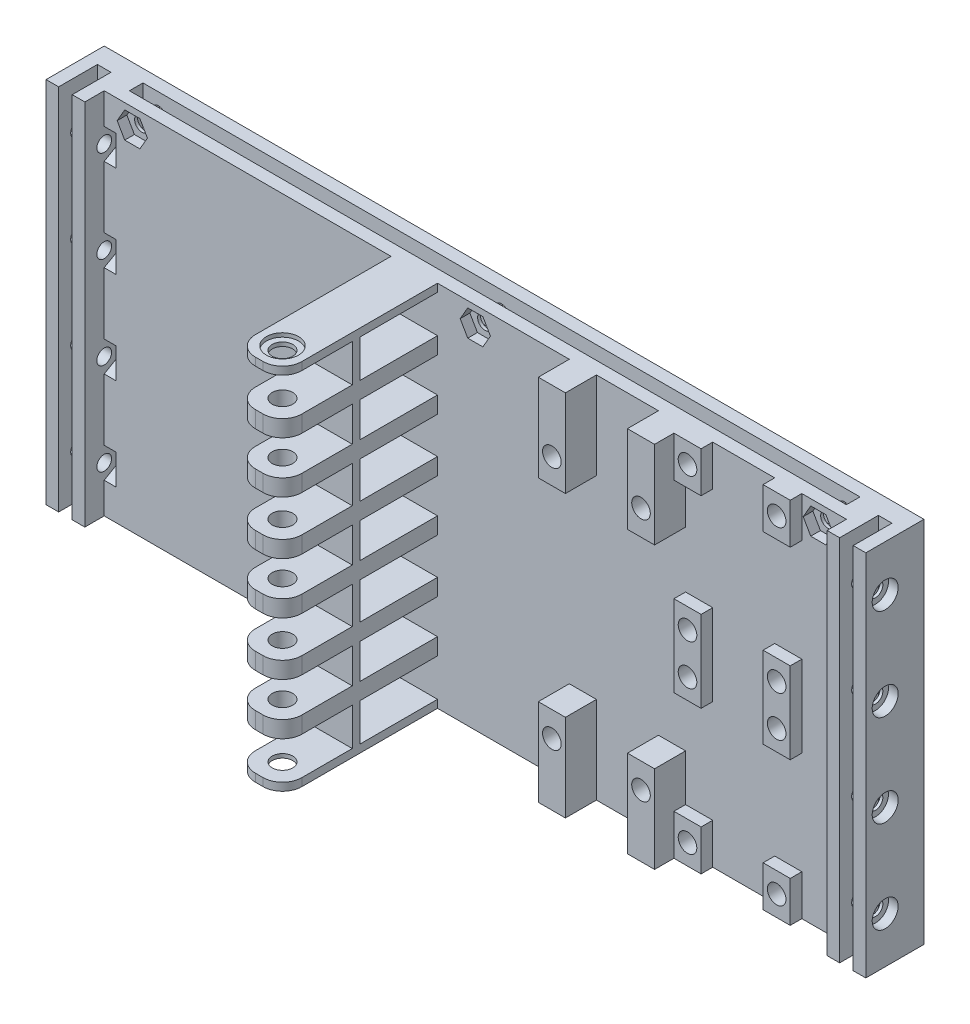
SolidWorks part; units mm, degrees
ref_plane "Front Plane" through (0, 0, 0) normal (1, 0, 0) x (0, 1, 0)
ref_plane "Top Plane" through (0, 0, 0) normal (0, 0, 1) x (0, 1, 0)
ref_plane "Right Plane" through (0, 0, 0) normal (0, 1, 0) x (-1, 0, 0)
sketch "Sketch1" plane through (0, 0, 0) normal (0, 0, 1) x (0, 1, 0)
  line L1 (0, 0) -> (-95, 0)
  line L2 (0, 0) -> (0, 12)
  line L3 (0, 12) -> (-95, 12)
  line L4 (-95, 0) -> (-95, 12)
extrude "Boss-Extrude1" add sketch "Sketch1" along normal blind 10 contours L3 L4 L1 L2
sketch "Sketch3" plane through (0, 0, 10) normal (0, 0, 1) x (1, 0, 0)
  line L0 (0, 0) -> (0, -95) construction
  line L1 (-12, 0) -> (0, 0)
  line L2 (-12, 0) -> (-12, -2.025)
  line L3 (-12, -2.025) -> (0, -2.025)
  line L4 (0, 0) -> (0, -2.025)
  line L6 (-12, -2.025) -> (0, -2.025) construction
  line L8 (-12, -11.725) -> (0, -11.725) construction
  line L10 (-12, -11.725) -> (0, -11.725)
  line L11 (-12, -11.725) -> (-12, -16.025)
  line L12 (-12, -16.025) -> (0, -16.025)
  line L13 (0, -11.725) -> (0, -16.025)
  line L14 (-12, -16.025) -> (0, -16.025) construction
  line L16 (-12, -24.975) -> (0, -24.975) construction
  line L18 (0, -24.975) -> (-12, -24.975)
  line L19 (0, -24.975) -> (0, -29.275)
  line L20 (0, -29.275) -> (-12, -29.275)
  line L21 (-12, -24.975) -> (-12, -29.275)
  line L23 (-12, -29.275) -> (0, -29.275) construction
  line L25 (-12, -38.725) -> (0, -38.725) construction
  line L27 (-12, -38.725) -> (0, -38.725)
  line L28 (-12, -38.725) -> (-12, -43.025)
  line L29 (-12, -43.025) -> (0, -43.025)
  line L30 (0, -38.725) -> (0, -43.025)
  dimension "D1" = 2.025
  dimension "D2" = 9.7
  dimension "D3" = 4.3
  dimension "D4" = 8.95
  dimension "D5" = 4.3
  dimension "D6" = 9.45
  dimension "D7" = 4.3
extrude "Boss-Extrude2" add sketch "Sketch3" along normal blind 40
fillet "Fillet1" radius 5 8 edges at (-12, -1.0125, 50) (0, -1.0125, 50) (-12, -13.875, 50) (0, -13.875, 50) (-12, -40.875, 50) (-12, -27.125, 50) (0, -27.125, 50) (0, -40.875, 50)
ref_plane "Plane1" through (0, -47.5, 0) normal (0, 1, 0) x (1, 0, 0)
mirror "Mirror1" about plane through (0, -47.5, 0) normal (0, 1, 0) of "Fillet1", "Boss-Extrude2"
sketch "Sketch5" plane through (0, 0, 0) normal (0, 1, 0) x (-1, 0, 0)
  line L0 (5, 50) -> (7, 50) construction
  line L1 (6, 50) -> (0, 50)
  line L2 (6, 50) -> (6, 44)
  line L3 (6, 44) -> (0, 44)
  line L4 (0, 50) -> (0, 44)
  circle A0 centre (6, 44) radius 2.65
  dimension "D2" = 5.3
  dimension "D1" = 6
extrude "Cut-Extrude1" cut sketch "Sketch5" against normal through all contours A0
sketch "Sketch7" plane through (0, 0, 0) normal (0, 1, 0) x (-1, 0, 0)
  line L0 (5, 50) -> (7, 50) construction
  line L1 (6, 50) -> (0, 50)
  line L2 (6, 50) -> (6, 44)
  line L3 (6, 44) -> (0, 44)
  line L4 (0, 50) -> (0, 44)
  line L5 (0, 45) -> (0, 0) construction
  circle A0 centre (6, 44) radius 4.15
  circle M6 centre (6, 44) radius 2.65
  dimension "D1" = 6
  dimension "D2" = 8.3
extrude "Cut-Extrude2" cut sketch "Sketch7" against normal blind 1 contours L3 A0 L2 M6 | L2 A0 L3 M6
mirror "Mirror2" about plane through (0, -47.5, 0) normal (0, 1, 0) of "Cut-Extrude2"
sketch "Sketch8" plane through (0, 0, 0) normal (0, 0, -1) x (1, 0, 0)
  line L0 (0, 95) -> (-12, 95) construction
  line L1 (-6, 95) -> (-96, 95)
  line L2 (-6, 95) -> (-6, 0)
  line L3 (-6, 0) -> (-96, 0)
  line L4 (-96, 95) -> (-96, 0)
  line L5 (-6, 95) -> (115.5, 95)
  line L6 (-6, 95) -> (-6, 0)
  line L7 (-6, 0) -> (115.5, 0)
  line L8 (115.5, 95) -> (115.5, 0)
  line L9 (0, 0) -> (-12, 0) construction
  line M2 (0, 0) -> (0, 95)
  line M4 (-12, 95) -> (-12, 0)
  dimension "D1" = 121.5
  dimension "D2" = 90
extrude "Boss-Extrude3" add sketch "Sketch8" against normal blind 10 contours L1 L4 L3 M4 | L8 L5 L7 M2
sketch "Sketch9" plane through (0, 0, 10) normal (0, 0, 1) x (1, 0, 0)
  line L0 (0, -95) -> (115.5, -95) construction
  line L1 (115.5, 0) -> (105.5, 0)
  line L2 (115.5, 0) -> (115.5, -95)
  line L3 (115.5, -95) -> (105.5, -95)
  line L4 (105.5, 0) -> (105.5, -95)
  line L5 (-12, -95) -> (-96, -95) construction
  line L6 (-96, 0) -> (-86, 0)
  line L7 (-96, 0) -> (-96, -95)
  line L8 (-96, -95) -> (-86, -95)
  line L9 (-86, 0) -> (-86, -95)
  dimension "D1" = 10
  dimension "D2" = 10
extrude "Boss-Extrude4" add sketch "Sketch9" along normal blind 5
sketch "Sketch12" plane through (-12, 0, 0) normal (-1, 0, 0) x (0, -1, 0)
  line L1 (0, 12) -> (95, 12)
  line L2 (0, 12) -> (0, 10)
  line L3 (0, 10) -> (95, 10)
  line L4 (95, 12) -> (95, 10)
  line L5 (95, 45) -> (95, 10) construction
  dimension "D1" = 2
sketch "Sketch11" plane through (0, 0, 15) normal (0, 0, 1) x (1, 0, 0)
  line L0 (110.5, 0) -> (110.5, -95) construction
  line L1 (115.5, 0) -> (105.5, 0) construction
  line L2 (105.5, -95) -> (115.5, -95) construction
  line L3 (110.5, -10) -> (110.5, -30) construction
  line L4 (112.5, -10) -> (112.5, -30)
  line L5 (108.5, -10) -> (108.5, -30)
  line L7 (115.5, 0) -> (110.5, 0)
  line L8 (115.5, 0) -> (115.5, -10)
  line L9 (115.5, -10) -> (110.5, -10)
  line L10 (110.5, 0) -> (110.5, -10)
  arc A0 (112.5, -10) -> (108.5, -10) centre (110.5, -10) ccw
  arc A1 (108.5, -30) -> (112.5, -30) centre (110.5, -30) ccw
  point P8 (110.5, -20)
  dimension "D1" = 10
  dimension "D2" = 20
extrude "Cut-Extrude3" [suppressed] cut sketch "Sketch11" against normal blind 10 contours L4 A1 L5 A0
pattern_linear "LPattern1" [suppressed] count 2 spacing 55
extrude "Boss-Extrude5" [suppressed] add sketch "Sketch12" along normal up to next
sketch "Sketch13" plane through (0, -95, 0) normal (0, 1, 0) x (-1, 0, 0)
  line L1 (0, 10) -> (12, 10)
  line L2 (0, 10) -> (0, 30)
  line L3 (0, 30) -> (12, 30)
  line L4 (12, 10) -> (12, 30)
  line L5 (12, 45) -> (12, 10) construction
  line L6 (0, 30) -> (12, 30)
  line L7 (0, 30) -> (0, 32)
  line L8 (0, 32) -> (12, 32)
  line L9 (12, 30) -> (12, 32)
  dimension "D1" = 20
  dimension "D2" = 2
extrude "Boss-Extrude6" add sketch "Sketch13" along normal through all contours L7 L6 L9 L8
sketch "Sketch14" plane through (0, 0, 0) normal (0, 1, 0) x (-1, 0, 0)
  line L0 (-115.5, 0) -> (96, 0) construction
  line L1 (86, 0) -> (-105.5, 0)
  line L2 (86, 0) -> (86, 10)
  line L3 (86, 10) -> (-105.5, 10)
  line L4 (-105.5, 0) -> (-105.5, 10)
  line L5 (82.75, 6.75) -> (-102.25, 6.75)
  line L6 (-102.25, 3.25) -> (-102.25, 6.75)
  line L7 (82.75, 3.25) -> (-102.25, 3.25)
  line L8 (82.75, 3.25) -> (82.75, 6.75)
  line L9 (96, 15) -> (96, 0) construction
  line L12 (96, 0) -> (86, 0)
  line L13 (96, 0) -> (96, 10)
  line L14 (96, 10) -> (86, 10)
  line L15 (86, 0) -> (86, 10)
  dimension "D1" = 3.25
extrude "Cut-Extrude4" cut sketch "Sketch14" against normal blind 10 contours L7 L8 L5 L6
mirror "Mirror3" about plane through (0, -47.5, 0) normal (0, 1, 0) of "Cut-Extrude4"
sketch "Sketch15" plane through (19.6145, 61.4983, 10) normal (0, 0, 1) x (1, 0, 0)
  line L1 (-105.6145, -61.4983) -> (-98.3645, -61.4983)
  line L2 (-105.6145, -61.4983) -> (-105.6145, -66.4983)
  line L3 (-105.6145, -66.4983) -> (-98.3645, -66.4983)
  line L4 (-98.3645, -61.4983) -> (-98.3645, -66.4983)
  circle A0 centre (-98.3645, -66.4983) radius 1.9
  circle A1 centre (-98.3645, -66.4983) radius 3.15
  dimension "D3" = 3.8
  dimension "D4" = 6.3
  dimension "D1" = 7.25
extrude "Cut-Extrude5" cut sketch "Sketch15" against normal through all contours A0
sketch "Sketch16" plane through (-19.6145, 61.4983, 0) normal (0, 0, -1) x (-1, 0, 0)
  circle A2 centre (59.1355, -66.4983) radius 3.35
  dimension "D1" = 6.7
extrude "Cut-Extrude6" cut sketch "Sketch16" against normal blind 2.5
sketch "Sketch17" plane through (19.6145, 61.4983, 10) normal (0, 0, 1) x (1, 0, 0)
  line L0 (-94.4604, -66.4983) -> (-96.4124, -63.1172)
  line L1 (-94.8645, -66.4983) -> (-96.6145, -63.4672)
  line L2 (-96.6145, -63.4672) -> (-100.1145, -63.4672)
  line L3 (-100.1145, -63.4672) -> (-101.8645, -66.4983)
  line L4 (-101.8645, -66.4983) -> (-100.1145, -69.5293)
  line L5 (-100.1145, -69.5293) -> (-96.6145, -69.5293)
  line L6 (-96.6145, -69.5293) -> (-94.8645, -66.4983)
  line L7 (-96.4124, -63.1172) -> (-100.3166, -63.1172)
  line L8 (-100.3166, -63.1172) -> (-102.2687, -66.4983)
  line L9 (-102.2687, -66.4983) -> (-100.3166, -69.8793)
  line L10 (-100.3166, -69.8793) -> (-96.4124, -69.8793)
  line L11 (-96.4124, -69.8793) -> (-94.4604, -66.4983)
  line L13 (-31.6145, -61.4983) -> (-105.6145, -61.4983) construction
  circle A0 centre (-98.3645, -66.4983) radius 3.0311 construction
  dimension "D1" = 3.5
  dimension "D2" = 0.35
extrude "Cut-Extrude7" cut sketch "Sketch17" against normal blind 2.5
pattern_linear "LPattern2" count 3 spacing 88.5 along (1, 0, 0) of "Cut-Extrude7", "Cut-Extrude6", "Cut-Extrude5"
sketch "Sketch18" plane through (0, 0, 10) normal (0, 0, 1) x (1, 0, 0)
  line L0 (0, -95) -> (105.5, -95) construction
  line L1 (105.5, 0) -> (94, 0)
  line L2 (105.5, 0) -> (105.5, -95)
  line L3 (105.5, -95) -> (94, -95)
  line L4 (94, 0) -> (94, -95)
  line L6 (94, 0) -> (87, 0)
  line L7 (94, 0) -> (94, -95)
  line L8 (94, -95) -> (87, -95)
  line L9 (87, 0) -> (87, -95)
  line L10 (87, 0) -> (71, 0)
  line L11 (87, 0) -> (87, -95)
  line L12 (87, -95) -> (71, -95)
  line L13 (71, 0) -> (71, -95)
  line L14 (71, 0) -> (64, 0)
  line L15 (71, 0) -> (71, -95)
  line L16 (71, -95) -> (64, -95)
  line L17 (64, 0) -> (64, -95)
  line L20 (64, 0) -> (64, -95)
  dimension "D1" = 11.5
  dimension "D2" = 7
  dimension "D3" = 16
  dimension "D4" = 7
extrude "Boss-Extrude7" add sketch "Sketch18" along normal blind 3
sketch "Sketch19" plane through (0, 0, 10) normal (0, 0, 1) x (1, 0, 0)
  line L0 (71, -95) -> (64, -95) construction
  line L4 (64, 0) -> (64, -95)
  line L6 (64, 0) -> (57, 0)
  line L7 (64, 0) -> (64, -95)
  line L8 (64, -95) -> (57, -95)
  line L9 (57, 0) -> (57, -95)
  line L10 (57, 0) -> (41, 0)
  line L11 (57, 0) -> (57, -95)
  line L12 (57, -95) -> (41, -95)
  line L13 (41, 0) -> (41, -95)
  line L14 (41, 0) -> (34, 0)
  line L15 (41, 0) -> (41, -95)
  line L16 (41, -95) -> (34, -95)
  line L17 (34, 0) -> (34, -95)
  line L18 (64, 0) -> (64, -95) construction
  dimension "D2" = 7
  dimension "D3" = 16
  dimension "D4" = 7
extrude "Boss-Extrude8" add sketch "Sketch19" along normal blind 8
sketch "Sketch20" plane through (0, 0, 0) normal (0, 1, 0) x (-1, 0, 0)
  line L0 (-112.25, 5) -> (-108.75, 5)
  line L1 (-115.5, 15) -> (-112.25, 15)
  line L2 (-115.5, 15) -> (-115.5, 5)
  line L3 (-115.5, 5) -> (-112.25, 5)
  line L4 (-112.25, 15) -> (-112.25, 5)
  line L5 (-105.5, 15) -> (-108.75, 15)
  line L6 (-105.5, 15) -> (-105.5, 5)
  line L7 (-105.5, 5) -> (-108.75, 5)
  line L8 (-108.75, 15) -> (-108.75, 5)
  dimension "D1" = 10
  dimension "D2" = 3.25
  dimension "D3" = 3.25
  dimension "D4" = 10
extrude "Cut-Extrude8" cut sketch "Sketch20" against normal up to next
pattern_linear "LPattern3" count 2 spacing 201.5 along (-1, 0, 0) of "Cut-Extrude8"
sketch "Sketch21" plane through (0, 0, 13) normal (0, 0, 1) x (1, 0, 0)
  line L1 (94, 0) -> (90.5, 0)
  line L2 (94, 0) -> (94, -5.25)
  line L3 (94, -5.25) -> (90.5, -5.25)
  line L4 (90.5, 0) -> (90.5, -5.25)
  line L5 (94, 0) -> (87, 0) construction
  circle A0 centre (90.5, -5.25) radius 2.4
  dimension "D2" = 4.8
  dimension "D1" = 5.25
extrude "Cut-Extrude9" cut sketch "Sketch21" against normal blind 3.8 contours A0
sketch "Sketch22" plane through (0, 0, 9.2) normal (0, 0, 1) x (1, 0, 0)
  circle A0 centre (90.5, -5.25) radius 1.75
  dimension "D1" = 3.5
extrude "Cut-Extrude10" cut sketch "Sketch22" against normal blind 0.6 contours A0
sketch "Sketch23" plane through (0, 0, 18) normal (0, 0, 1) x (1, 0, 0)
  line L0 (64, 0) -> (57, 0) construction
  line L1 (64, 0) -> (60.5, 0)
  line L2 (64, 0) -> (64, -16)
  line L3 (64, -16) -> (60.5, -16)
  line L4 (60.5, 0) -> (60.5, -16)
  line L6 (64, -95) -> (64, 0) construction
  circle A0 centre (60.5, -16) radius 2.4
  dimension "D2" = 4.8
  dimension "D1" = 16
extrude "Cut-Extrude11" cut sketch "Sketch23" against normal blind 3.8 contours A0
sketch "Sketch24" plane through (0, 0, 14.2) normal (0, 0, 1) x (1, 0, 0)
  circle A0 centre (60.5, -16) radius 1.75
  dimension "D1" = 3.5
extrude "Cut-Extrude12" cut sketch "Sketch24" against normal blind 0.6 contours A0
pattern_linear "LPattern4" count 2 spacing 23 along (-1, 0, 0) count 2 spacing 37 along (0, -1, 0) of "Cut-Extrude10", "Cut-Extrude9"
pattern_linear "LPattern5" count 2 spacing 23 along (-1, 0, 0) of "Cut-Extrude11", "Cut-Extrude12"
mirror "Mirror4" about plane through (0, -47.5, 0) normal (0, 1, 0) of "LPattern5", "LPattern4", "Cut-Extrude9", "Cut-Extrude10", "Cut-Extrude11", "Cut-Extrude12"
sketch "Sketch25" plane through (115.5, 0, 0) normal (1, 0, 0) x (0, 1, 0)
  line L1 (0, 15) -> (-11.875, 15)
  line L2 (0, 15) -> (0, 10)
  line L3 (0, 10) -> (-11.875, 10)
  line L4 (-11.875, 15) -> (-11.875, 10)
  circle A0 centre (-11.875, 10) radius 1.9
  dimension "D2" = 3.8
  dimension "D3" = 11.875
extrude "Cut-Extrude13" cut sketch "Sketch25" against normal blind 10 contours A0
sketch "Sketch26" plane through (115.5, 0, 0) normal (1, 0, 0) x (0, 1, 0)
  circle A0 centre (-11.875, 10) radius 3.35
  dimension "D1" = 6.7
extrude "Cut-Extrude14" cut sketch "Sketch26" against normal blind 2.5
sketch "Sketch27" plane through (105.5, 0, 0) normal (-1, 0, 0) x (0, -1, 0)
  line L0 (0, 15) -> (95, 15) construction
  line L1 (10.125, 13.0311) -> (8.375, 10)
  line L2 (8.375, 10) -> (10.125, 6.9689)
  line L3 (10.125, 6.9689) -> (13.625, 6.9689)
  line L4 (13.625, 6.9689) -> (15.375, 10)
  line L5 (15.375, 10) -> (13.625, 13.0311)
  line L6 (13.625, 13.0311) -> (10.125, 13.0311)
  line L7 (9.9229, 13.3811) -> (7.9709, 10)
  line L8 (7.9709, 10) -> (9.9229, 6.6189)
  line L9 (9.9229, 6.6189) -> (13.8271, 6.6189)
  line L10 (13.8271, 6.6189) -> (15.7791, 10)
  line L11 (15.7791, 10) -> (13.8271, 13.3811)
  line L12 (13.8271, 13.3811) -> (9.9229, 13.3811)
  circle A0 centre (11.875, 10) radius 3.0311 construction
  dimension "D1" = 3.5
  dimension "D2" = 0.35
extrude "Cut-Extrude15" cut sketch "Sketch27" along normal blind 3 contours L11 L12 L7 L8 L9 L10
pattern_linear "LPattern6" count 4 spacing 23.75 along (0, -1, 0) of "Cut-Extrude14", "Cut-Extrude15", "Cut-Extrude13"
ref_plane "Plane2" through (9.75, 0, 0) normal (1, 0, 0) x (0, 0, -1)
mirror "Mirror5" about plane through (9.75, 0, 0) normal (1, 0, 0) of "LPattern6", "Cut-Extrude13", "Cut-Extrude14", "Cut-Extrude15"
sketch "Sketch28" plane through (34, 0, 0) normal (-1, 0, 0) x (0, -1, 0)
  line L0 (0, 10) -> (95, 10) construction
  line L1 (0, 18) -> (22.5, 18)
  line L2 (0, 18) -> (0, 10)
  line L3 (0, 10) -> (22.5, 10)
  line L4 (22.5, 18) -> (22.5, 10)
  line L6 (22.5, 18) -> (72.5, 18)
  line L8 (22.5, 10) -> (72.5, 10)
  line L9 (72.5, 18) -> (72.5, 10)
  line L10 (72.5, 18) -> (95, 18)
  line L12 (72.5, 10) -> (95, 10)
  line L13 (95, 18) -> (95, 10)
  line M6 (0, 10) -> (95, 10)
  line M8 (95, 18) -> (0, 18)
  dimension "D1" = 22.5
  dimension "D2" = 22.5
extrude "Cut-Extrude16" cut sketch "Sketch28" against normal blind 30 contours L9 L4 M8 M6
sketch "Sketch29" plane through (64, 0, 0) normal (-1, 0, 0) x (0, -1, 0)
  line L0 (0, 13) -> (95, 13) construction
  line L1 (0, 10) -> (10.5, 10)
  line L2 (0, 10) -> (0, 13)
  line L3 (0, 13) -> (10.5, 13)
  line L4 (10.5, 10) -> (10.5, 13)
  line L6 (10.5, 13) -> (37, 13)
  line L7 (10.5, 13) -> (10.5, 10)
  line L8 (10.5, 10) -> (37, 10)
  line L9 (37, 13) -> (37, 10)
  line L10 (0, 10) -> (95, 10) construction
  line L11 (37, 13) -> (58, 13)
  line L12 (37, 13) -> (37, 10)
  line L13 (37, 10) -> (58, 10)
  line L14 (58, 13) -> (58, 10)
  line L15 (58, 13) -> (84.5, 13)
  line L16 (58, 13) -> (58, 10)
  line L17 (58, 10) -> (84.5, 10)
  line L18 (84.5, 13) -> (84.5, 10)
  line L20 (84.5, 13) -> (95, 13)
  line L21 (84.5, 13) -> (84.5, 10)
  line L22 (84.5, 10) -> (95, 10)
  line L23 (95, 13) -> (95, 10)
  line M15 (22.5, 13) -> (22.5, 10)
  line M16 (22.5, 10) -> (72.5, 10)
  line M17 (72.5, 10) -> (72.5, 13)
  line M18 (72.5, 13) -> (22.5, 13)
  dimension "D1" = 10.5
  dimension "D2" = 10.5
  dimension "D3" = 26.5
  dimension "D4" = 26.5
extrude "Cut-Extrude17" cut sketch "Sketch29" against normal blind 30 contours L4 L8 L6 M15 | L9 M18 M15 M16 | L18 L15 L17 M17 | L14 M18 M16 M17
equation "\"whitekey_cutout_length\"= 101.5"
equation "\"wall_thickness\"=10"
equation "\"D1@Sketch9\"=\"wall_thickness\""
equation "\"D2@Sketch9\"=\"wall_thickness\""
equation "\"D1@Boss-Extrude3\"=\"wall_thickness\""
equation "\"base_mount_height\"=40"
equation "\"D1@Boss-Extrude2\"=\"base_mount_height\""
equation "\"base_rear_length\"=80"
equation "\"D1@Sketch8\"=\"wall_thickness\"+110+1.5"
equation "\"D2@Sketch8\"=\"base_rear_length\"+\"wall_thickness\""
equation "\"key_mount_recess_length\"=50"
equation "\"key_mount_recess_height\"=12.5"
equation "\"key_mount_recess_depth\"=1.5"
equation "\"guide_brace_height\"=20"
equation "\"guide_brace_thickness\"=2"
equation "\"dowel_recess_depth\"=10"
equation "\"dowel_recess_offset\"=3.25"
equation "\"base_front_length\"=111.5"
equation "\"screw_hole_wall_offset\"=7.25"
equation "\"screw_hole_edge_inset\"=\"dowel_recess_depth\"/2"
equation "\"screw_hole_diameter\"=3.8"
equation "\"screw_head_hole_diameter\"=6.7"
equation "\"screw_nut_hole_side_len\"=3.5"
equation "\"screw_nut_recess_offset\"=0.35"
equation "\"screw_head_and_nut_recess_depth\"=2.5"
equation "\"screw_shaft_diameter\"=3.5"
equation "\"switch_board_width\"=30"
equation "\"switch_board_thickness\"=1.6"
equation "\"switch_board_wall_offset\"=11.5"
equation "\"heatset_insert_hole_diameter\"=4.8"
equation "\"heatset_insert_hole_depth\"=3.8"
equation "\"front_rear_panel_width\"=23.75"
equation "\"rod_length_adj\"=0.5"
equation "\"rod_insert_length\"=2.8"
equation "\"D1@Sketch14\"=\"dowel_recess_offset\""
equation "\"D1@Cut-Extrude4\"=\"dowel_recess_depth\""
equation "\"D1@Sketch13\"=\"guide_brace_height\""
equation "\"D2@Sketch13\"=\"guide_brace_thickness\""
equation "\"D1@Sketch15\"=\"screw_hole_wall_offset\""
equation "\"D2@Sketch15\"=\"screw_hole_edge_inset\""
equation "\"D3@Sketch15\"=\"screw_hole_diameter\""
equation "\"D1@Sketch16\"=\"screw_head_hole_diameter\""
equation "\"D1@Cut-Extrude6\"=\"screw_head_and_nut_recess_depth\""
equation "\"D1@Sketch17\"=\"screw_nut_hole_side_len\""
equation "\"D2@Sketch17\"=\"screw_nut_recess_offset\""
equation "\"D3@LPattern2\"=0.5*(\"base_front_length\"+\"base_rear_length\"-\"screw_hole_wall_offset\"*2)"
equation "\"D1@Sketch18\"=\"switch_board_wall_offset\""
equation "\"D2@Sketch18\"=\"screw_shaft_diameter\"*2"
equation "\"D3@Sketch18\"=\"switch_board_width\"-\"screw_shaft_diameter\"*4"
equation "\"D4@Sketch18\"=\"screw_shaft_diameter\"*2"
equation "\"D1@Boss-Extrude7\"=\"switch_white_key_mount_height\""
equation "\"D2@Sketch19\"=\"screw_shaft_diameter\"*2"
equation "\"D3@Sketch19\"=\"switch_board_width\"-\"screw_shaft_diameter\"*4"
equation "\"D4@Sketch19\"=\"screw_shaft_diameter\"*2"
equation "\"D1@Boss-Extrude8\"=\"switch_black_key_mount_height\""
equation "\"switch_black_key_mount_height\"=8"
equation "\"switch_white_key_mount_height\"=3"
equation "\"D1@Sketch20\"=\"dowel_recess_depth\""
equation "\"D2@Sketch20\"=\"dowel_recess_offset\""
equation "\"D3@Sketch20\"=\"dowel_recess_offset\""
equation "\"D4@Sketch20\"=\"dowel_recess_depth\""
equation "\"D3@LPattern3\"=\"base_front_length\"+\"base_rear_length\"+\"wall_thickness\""
equation "\"D2@Sketch21\"=\"heatset_insert_hole_diameter\""
equation "\"D1@Cut-Extrude9\"=\"heatset_insert_hole_depth\""
equation "\"D1@Sketch22\"=\"screw_shaft_diameter\""
equation "\"D1@Cut-Extrude10\"=6-\"heatset_insert_hole_depth\"-\"switch_board_thickness\""
equation "\"D2@Sketch23\"=\"heatset_insert_hole_diameter\""
equation "\"D1@Cut-Extrude11\"=\"heatset_insert_hole_depth\""
equation "\"D1@Sketch24\"=\"screw_shaft_diameter\""
equation "\"D1@Cut-Extrude12\"=6-\"heatset_insert_hole_depth\"-\"switch_board_thickness\""
equation "\"D3@LPattern4\"=\"switch_board_width\"-\"screw_shaft_diameter\"*2"
equation "\"D3@LPattern5\"=\"switch_board_width\"-\"screw_shaft_diameter\"*2"
equation "\"D1@Sketch25\"=\"screw_hole_edge_inset\""
equation "\"D3@Sketch25\"=\"front_rear_panel_width\"/2"
equation "\"D2@Sketch25\"=\"screw_hole_diameter\""
equation "\"D1@Cut-Extrude13\"=\"wall_thickness\""
equation "\"D1@Sketch26\"=\"screw_head_hole_diameter\""
equation "\"D1@Cut-Extrude14\"=\"screw_head_and_nut_recess_depth\""
equation "\"D1@Sketch27\"=\"screw_nut_hole_side_len\""
equation "\"D2@Sketch27\"=\"screw_nut_recess_offset\""
equation "\"D1@Cut-Extrude15\"=\"screw_head_and_nut_recess_depth\"+0.5"
equation "\"D3@LPattern6\"=\"front_rear_panel_width\""
equation "\"D1@Cut-Extrude16\"=\"switch_board_width\""
equation "\"D1@Cut-Extrude17\"=\"switch_board_width\""
equation "\"rod_diameter\"=5"
equation "\"rod_head_diameter\"=8"
equation "\"D2@Sketch5\"=\"rod_diameter\"+0.3"
equation "\"D2@Sketch7\"=\"rod_head_diameter\"+0.3"
equation "\"D1@Boss-Extrude4\"=\"wall_thickness\"/2"
